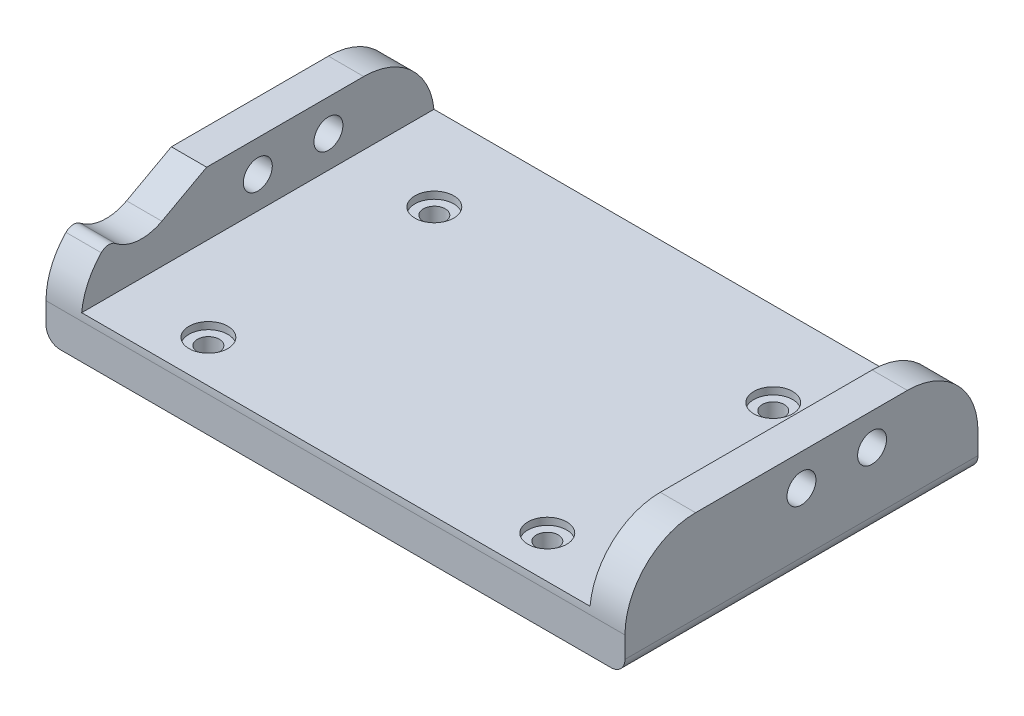
SolidWorks part; units mm, degrees
material "PLA"
ref_plane "Front Plane" through (0, 0, 0) normal (0, 0, 1) x (1, 0, 0)
ref_plane "Top Plane" through (0, 0, 0) normal (0, 1, 0) x (1, 0, 0)
ref_plane "Right Plane" through (0, 0, 0) normal (1, 0, 0) x (0, 0, -1)
sketch "Sketch1" plane through (0, 0, 0) normal (0, 1, 0) x (1, 0, 0)
  line L0 (0, 0) -> (-71.0876, 0) construction
  line L1 (-36, 20) -> (36, 20)
  line L2 (-36, 20) -> (-36, -20)
  line L3 (-36, -20) -> (36, -20)
  line L4 (36, 20) -> (36, -20)
  line L5 (-36, 20) -> (36, -20) construction
  line L6 (-36, -20) -> (36, 20) construction
  line L10 (0, 0) -> (0, 47.7981) construction
  point P0 (0, 0)
  dimension "D1" = 40
  dimension "D2" = 72
extrude "Boss-Extrude1" add sketch "Sketch1" along normal blind 6
sketch "Sketch3" plane through (36, 0, 0) normal (1, 0, 0) x (0, 0, -1)
  line L0 (20, 6) -> (20, 0) construction
  line L1 (-20, 0) -> (20, 0)
  line L2 (-20, 0) -> (-20, 15)
  line L3 (-20, 15) -> (20, 15)
  line L4 (20, 0) -> (20, 15)
  line L5 (-20, 6) -> (20, 6) construction
  line L6 (0, 0) -> (0, 15) construction
  circle A0 centre (-5, 10.5) radius 2.05
  circle A1 centre (5, 10.5) radius 2.05
  dimension "D1" = 4.1
  dimension "D2" = 4.5
  dimension "D3" = 10
  dimension "D4" = 4.5
extrude "Boss-Extrude2" add sketch "Sketch3" along normal blind 5
ref_plane "Plane1" through (0, 0, 0) normal (-1, 0, 0) x (0, 0, 1)
mirror "Mirror1" about plane through (0, 0, 0) normal (-1, 0, 0) of "Boss-Extrude2"
fillet "Fillet2" radius 10 1 edges at (38.5, 15, -20)
fillet "Fillet1" radius 2 2 edges at (41, 0, 0) (-41, 0, 0)
sketch "Sketch5" plane through (0, 0, 20) normal (0, 0, 1) x (1, 0, 0)
  line L4 (-41, 15) -> (-41, 2)
  line L5 (-39, 0) -> (39, 0)
  line L6 (41, 2) -> (41, 15)
  line L7 (41, 15) -> (36, 15)
  line L8 (-41, 15) -> (-41, 2)
  line L9 (-39, 0) -> (39, 0)
  line L10 (41, 2) -> (41, 15)
  line L16 (41, 15) -> (36, 15)
  line L17 (36, 15) -> (36, 6)
  line L18 (36, 15) -> (36, 6)
  line L19 (36, 6) -> (-36, 6)
  line L20 (36, 6) -> (-36, 6)
  line L21 (-36, 6) -> (-36, 15)
  line L22 (-36, 6) -> (-36, 15)
  line L23 (-36, 15) -> (-41, 15)
  line L24 (-36, 15) -> (-41, 15)
  arc A2 (-41, 2) -> (-39, 0) centre (-39, 2) ccw
  arc A3 (39, 0) -> (41, 2) centre (39, 2) ccw
  arc A4 (-41, 2) -> (-39, 0) centre (-39, 2) ccw
  arc A5 (39, 0) -> (41, 2) centre (39, 2) ccw
  dimension "D1" = 0
extrude "Boss-Extrude3" add sketch "Sketch5" along normal blind 10
sketch "Sketch6" plane through (0, 0, 0) normal (0, -1, 0) x (1, 0, 0)
  line L0 (39, -20) -> (-39, -20) construction
  line L1 (0, 0) -> (0, 21.7838) construction
  circle A0 centre (24, 24) radius 1.55
  circle A1 centre (24, -8) radius 1.55
  circle A2 centre (-24, 24) radius 1.55
  circle A3 centre (-24, -8) radius 1.55
  point P10 (0, 0)
  dimension "D1" = 3.1
  dimension "D2" = 32
  dimension "D3" = 48
  dimension "D4" = 12
extrude "Cut-Extrude2" cut sketch "Sketch6" against normal blind 10
sketch "Sketch2" plane through (0, 6, 0) normal (0, 1, 0) x (1, 0, 0)
  circle A0 centre (-24, 8) radius 2.75
  circle A1 centre (-24, -24) radius 2.75
  circle A2 centre (24, -24) radius 2.75
  circle A3 centre (24, 8) radius 2.75
  point P12 (-24, -16)
  point P13 (0, 0)
  point P14 (0, 0)
  point P15 (0, 0)
  point P16 (0, 0)
  point P17 (-24, -24)
  point P19 (24, -24)
  point P21 (24, 8)
  point P23 (-24, 8)
  dimension "D1" = 5.5
extrude "Cut-Extrude1" cut sketch "Sketch2" against normal blind 1
fillet "Fillet3" radius 10 1 edges at (-38.5, 15, 30)
sketch "Sketch7" plane through (-41, 0, 0) normal (-1, 0, 0) x (0, 0, 1)
  line L0 (12.2454, 15) -> (18.5892, 11.5463)
  line L6 (14.4785, 30.2338) -> (-20.1262, 62.7452)
  line L7 (-46.7425, 30.2338) -> (-49.3466, 9.383)
  line L8 (-47.8557, 4.4465) -> (-46.373, 3.1042)
  line L9 (-19.0387, -10.3694) -> (-20.8969, 6.5026)
  line L10 (-10, 16) -> (12.5, 16)
  line L11 (12.5, 16) -> (19.0673, 12.4245)
  line L12 (14.4785, 30.2338) -> (-20.1262, 62.7452)
  line L13 (-46.7425, 30.2338) -> (-49.3466, 9.383)
  line L14 (-47.8557, 4.4465) -> (-46.373, 3.1042)
  line L15 (-19.0387, -10.3694) -> (-20.8969, 6.5026)
  line L16 (-10, 16) -> (12.5, 16)
  line L17 (12.5, 16) -> (19.0673, 12.4245)
  line L22 (30, 2) -> (30, 5)
  line L23 (20, 15) -> (-10, 15)
  line L24 (-20, 5) -> (-20, 2)
  line L25 (-20, 2) -> (30, 2)
  line L27 (20, 15) -> (-10, 15)
  line L28 (-20, 5) -> (-20, 2)
  line L29 (-20, 2) -> (-19.395, 2)
  line L52 (-20, 5) -> (-19.4493, 0)
  line L53 (30, 0) -> (-20, 0) construction
  line L54 (-19.4493, 0) -> (-20.1807, 0)
  line L55 (-20, 5) -> (-20.7314, 5)
  line L90 (-57.5711, -13.7362) -> (-55.4178, -15.6855)
  line L91 (-57.5711, -13.7362) -> (-55.4178, -15.6855)
  line L92 (-52.5924, -14.1966) -> (-52.047, -13.5942)
  line L93 (-52.5924, -14.1966) -> (-52.047, -13.5942)
  line L94 (-51.1244, -12.575) -> (-50.0337, -11.3701)
  line L95 (-51.1244, -12.575) -> (-50.0337, -11.3701)
  line L96 (-49.1111, -10.3509) -> (-48.0203, -9.146)
  line L97 (-49.1111, -10.3509) -> (-48.0203, -9.146)
  line L98 (-47.0977, -8.1268) -> (-46.007, -6.922)
  line L99 (-47.0977, -8.1268) -> (-46.007, -6.922)
  line L100 (-45.0844, -5.9028) -> (-43.9937, -4.6979)
  line L101 (-45.0844, -5.9028) -> (-43.9937, -4.6979)
  line L102 (-43.0711, -3.6787) -> (-41.1835, -1.5935)
  line L103 (-43.0711, -3.6787) -> (-41.1835, -1.5935)
  line L104 (-41.1835, -1.5935) -> (-34.0665, -8.0362)
  line L105 (-41.1835, -1.5935) -> (-34.0665, -8.0362)
  line L106 (-34.0665, -8.0362) -> (-35.954, -10.1213)
  line L107 (-34.0665, -8.0362) -> (-35.954, -10.1213)
  line L108 (-36.8767, -11.1405) -> (-37.9674, -12.3454)
  line L109 (-36.8767, -11.1405) -> (-37.9674, -12.3454)
  line L110 (-38.89, -13.3646) -> (-39.9807, -14.5695)
  line L111 (-38.89, -13.3646) -> (-39.9807, -14.5695)
  line L112 (-40.9033, -15.5887) -> (-41.994, -16.7936)
  line L113 (-40.9033, -15.5887) -> (-41.994, -16.7936)
  line L114 (-42.9166, -17.8128) -> (-44.0074, -19.0176)
  line L115 (-42.9166, -17.8128) -> (-44.0074, -19.0176)
  line L116 (-44.93, -20.0368) -> (-45.4753, -20.6393)
  line L117 (-44.93, -20.0368) -> (-45.4753, -20.6393)
  line L118 (-46.6765, -23.5985) -> (-44.5232, -25.5478)
  line L119 (-46.6765, -23.5985) -> (-44.5232, -25.5478)
  line L120 (-44.5232, -25.5478) -> (-33.1144, -12.9447)
  line L121 (-44.5232, -25.5478) -> (-33.1144, -12.9447)
  line L122 (-28.877, -12.734) -> (-27.3942, -14.0762)
  line L123 (-28.877, -12.734) -> (-27.3942, -14.0762)
  line L124 (31.601, 13.7254) -> (32.6504, 11.7513)
  line L125 (31.601, 13.7254) -> (32.6504, 11.7513)
  line L126 (32.4548, 23.1648) -> (14.4785, 30.2338)
  line L127 (32.4548, 23.1648) -> (14.4785, 30.2338)
  line L128 (-46.1622, -1.1332) -> (-57.5711, -13.7362)
  line L129 (-46.1622, -1.1332) -> (-57.5711, -13.7362)
  arc A0 (18.5892, 11.5463) -> (25.5664, 21.1887) centre (21.4581, 16.8159) ccw
  arc A6 (19.0673, 12.4245) -> (26.4581, 16.8159) centre (21.4581, 16.8159) ccw
  arc A7 (-20.1262, 62.7452) -> (-23.4838, 61.5048) centre (-21.4957, 61.2876) ccw
  arc A8 (-46.7425, 30.2338) -> (-23.4838, 61.5048) centre (-61.7561, 65.6858) ccw
  arc A9 (-49.3466, 9.383) -> (-47.8557, 4.4465) centre (-44.5002, 8.1532) ccw
  arc A10 (-27.3942, -14.0762) -> (-19.0387, -10.3694) centre (-24.0387, -10.3694) ccw
  arc A11 (-10, 16) -> (-20.8969, 6.5026) centre (-10, 5) ccw
  arc A12 (19.0673, 12.4245) -> (26.4581, 16.8159) centre (21.4581, 16.8159) ccw
  arc A13 (-20.1262, 62.7452) -> (-23.4838, 61.5048) centre (-21.4957, 61.2876) ccw
  arc A14 (-46.7425, 30.2338) -> (-23.4838, 61.5048) centre (-61.7561, 65.6858) ccw
  arc A15 (-49.3466, 9.383) -> (-47.8557, 4.4465) centre (-44.5002, 8.1532) ccw
  arc A16 (-27.3942, -14.0762) -> (-19.0387, -10.3694) centre (-24.0387, -10.3694) ccw
  arc A17 (-10, 16) -> (-20.8969, 6.5026) centre (-10, 5) ccw
  arc A20 (30, 5) -> (20, 15) centre (20, 5) ccw
  arc A21 (-10, 15) -> (-20, 5) centre (-10, 5) ccw
  arc A22 (26.0543, 12.959) -> (20, 15) centre (20, 5) ccw
  arc A23 (-10, 15) -> (-20, 5) centre (-10, 5) ccw
  arc A47 (-28.877, -12.734) -> (-33.1144, -12.9447) centre (-30.8903, -14.958) ccw
  arc A48 (-28.877, -12.734) -> (-33.1144, -12.9447) centre (-30.8903, -14.958) ccw
  arc A49 (-46.1622, -1.1332) -> (-46.373, 3.1042) centre (-48.3863, 0.8802) ccw
  arc A50 (-46.1622, -1.1332) -> (-46.373, 3.1042) centre (-48.3863, 0.8802) ccw
  arc A80 (-55.4178, -15.6855) -> (-55.0854, -15.5104) centre (-55.2836, -15.5372) ccw
  arc A81 (-55.4178, -15.6855) -> (-55.0854, -15.5104) centre (-55.2836, -15.5372) ccw
  arc A82 (-52.5924, -14.1966) -> (-55.0854, -15.5104) centre (-53.599, -15.3086) ccw
  arc A83 (-52.5924, -14.1966) -> (-55.0854, -15.5104) centre (-53.599, -15.3086) ccw
  arc A84 (-51.1244, -12.575) -> (-52.047, -13.5942) centre (-51.9564, -12.749) ccw
  arc A85 (-51.1244, -12.575) -> (-52.047, -13.5942) centre (-51.9564, -12.749) ccw
  arc A86 (-49.1111, -10.3509) -> (-50.0337, -11.3701) centre (-49.943, -10.5249) ccw
  arc A87 (-49.1111, -10.3509) -> (-50.0337, -11.3701) centre (-49.943, -10.5249) ccw
  arc A88 (-47.0977, -8.1268) -> (-48.0203, -9.146) centre (-47.9297, -8.3009) ccw
  arc A89 (-47.0977, -8.1268) -> (-48.0203, -9.146) centre (-47.9297, -8.3009) ccw
  arc A90 (-45.0844, -5.9028) -> (-46.007, -6.922) centre (-45.9164, -6.0768) ccw
  arc A91 (-45.0844, -5.9028) -> (-46.007, -6.922) centre (-45.9164, -6.0768) ccw
  arc A92 (-43.0711, -3.6787) -> (-43.9937, -4.6979) centre (-43.9031, -3.8527) ccw
  arc A93 (-43.0711, -3.6787) -> (-43.9937, -4.6979) centre (-43.9031, -3.8527) ccw
  arc A94 (-36.8767, -11.1405) -> (-35.954, -10.1213) centre (-36.0447, -10.9665) ccw
  arc A95 (-36.8767, -11.1405) -> (-35.954, -10.1213) centre (-36.0447, -10.9665) ccw
  arc A96 (-38.89, -13.3646) -> (-37.9674, -12.3454) centre (-38.058, -13.1906) ccw
  arc A97 (-38.89, -13.3646) -> (-37.9674, -12.3454) centre (-38.058, -13.1906) ccw
  arc A98 (-40.9033, -15.5887) -> (-39.9807, -14.5695) centre (-40.0713, -15.4146) ccw
  arc A99 (-40.9033, -15.5887) -> (-39.9807, -14.5695) centre (-40.0713, -15.4146) ccw
  arc A100 (-42.9166, -17.8128) -> (-41.994, -16.7936) centre (-42.0847, -17.6387) ccw
  arc A101 (-42.9166, -17.8128) -> (-41.994, -16.7936) centre (-42.0847, -17.6387) ccw
  arc A102 (-44.93, -20.0368) -> (-44.0074, -19.0176) centre (-44.098, -19.8628) ccw
  arc A103 (-44.93, -20.0368) -> (-44.0074, -19.0176) centre (-44.098, -19.8628) ccw
  arc A104 (-46.5352, -23.2504) -> (-45.4753, -20.6393) centre (-46.482, -21.7513) ccw
  arc A105 (-46.5352, -23.2504) -> (-45.4753, -20.6393) centre (-46.482, -21.7513) ccw
  arc A106 (-46.5352, -23.2504) -> (-46.6765, -23.5985) centre (-46.5423, -23.4502) ccw
  arc A107 (-46.5352, -23.2504) -> (-46.6765, -23.5985) centre (-46.5423, -23.4502) ccw
  arc A108 (31.601, 13.7254) -> (26.4581, 16.8159) centre (29.9581, 16.8159) ccw
  arc A109 (31.601, 13.7254) -> (26.4581, 16.8159) centre (29.9581, 16.8159) ccw
  arc A110 (32.6504, 11.7513) -> (34.1474, 11.4315) centre (33.5334, 12.2207) ccw
  arc A111 (32.6504, 11.7513) -> (34.1474, 11.4315) centre (33.5334, 12.2207) ccw
  arc A112 (34.1474, 11.4315) -> (32.4548, 23.1648) centre (29.9581, 16.8159) ccw
  arc A113 (34.1474, 11.4315) -> (32.4548, 23.1648) centre (29.9581, 16.8159) ccw
  arc M34 (30, 5) -> (20, 15) centre (20, 5) ccw
  line M35 (20, 15) -> (-10, 15)
  line M37 (-20, 5) -> (-20, 2)
  line M38 (-20, 2) -> (30, 2)
  dimension "D1" = 0
  dimension "D3" = 0
extrude "Cut-Extrude3" cut sketch "Sketch7" against normal blind 7 contours L17 A12 M34 M35 | A12 L17 L0 A0 M35 M34 | L55 L15 L54 L52 M37 M38 | L52 M37 M38 region at (-41, 14.8557, 13.2911) region at (-41, 13.6214, 20.4154) region at (-41, 3, -19.8899) region at (-41, 2.4216, -20.1218)
fillet "Fillet4" radius 1.5 1 edges at (-38.5, 12.959, 26.0543)
